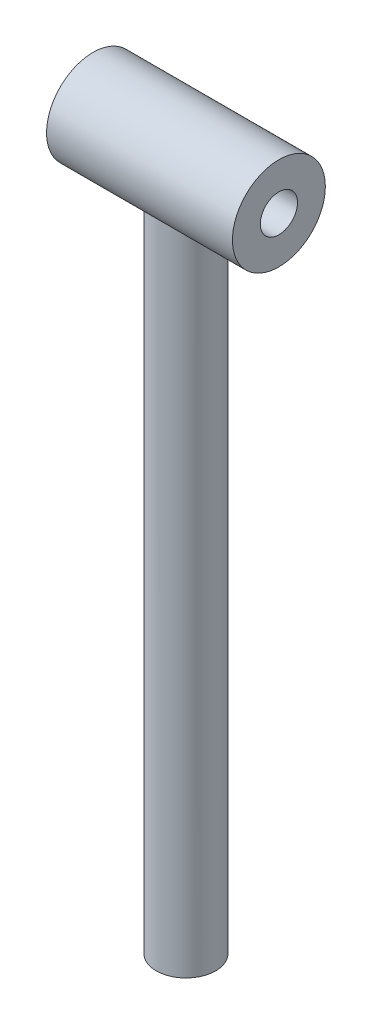
SolidWorks part; units mm, degrees
material "3.0515 (EN-AW 3103)"
ref_plane "Płaszczyzna przednia" through (0, 0, 0) normal (0, 0, 1) x (1, 0, 0)
ref_plane "Płaszczyzna górna" through (0, 0, 0) normal (0, 1, 0) x (1, 0, 0)
ref_plane "Płaszczyzna prawa" through (0, 0, 0) normal (1, 0, 0) x (0, 0, -1)
sketch "Szkic2" plane through (0, 0, 0) normal (1, 0, 0) x (0, 0, -1)
  circle A0 centre (0, 0) radius 12.5
  circle A1 centre (0, 0) radius 5
  dimension "D1" = 10
  dimension "D2" = 25
extrude "Dodanie-wyciągnięcie1" add sketch "Szkic2" along normal blind 25 and the other way blind 25
ref_plane "Płaszczyzna1" through (0, -5, 0) normal (0, 1, 0) x (1, 0, 0)
sketch "Szkic3" plane through (0, -5, 0) normal (0, 1, 0) x (1, 0, 0)
  circle A0 centre (0, 0) radius 8
  dimension "D1" = 16
extrude "Dodanie-wyciągnięcie2" add sketch "Szkic3" against normal blind 180
